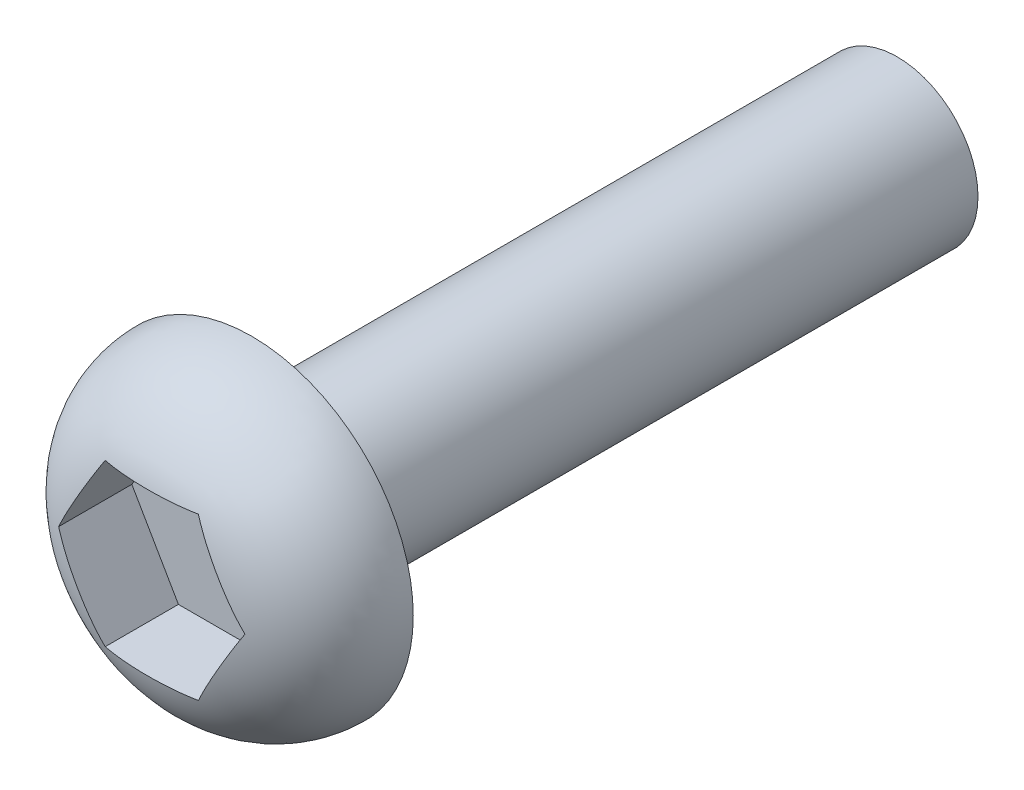
SolidWorks part; units mm, degrees
material "AISI 316 Stainless Steel Sheet (SS)"
ref_plane "Front Plane" through (0, 0, 0) normal (0, 0, 1) x (1, 0, 0)
ref_plane "Top Plane" through (0, 0, 0) normal (0, 1, 0) x (1, 0, 0)
ref_plane "Right Plane" through (0, 0, 0) normal (1, 0, 0) x (0, 0, -1)
sketch "Sketch1" plane through (0, 0, 0) normal (0, 0, 1) x (1, 0, 0)
  circle A0 centre (0, 0) radius 1.5
extrude "Boss-Extrude1" add sketch "Sketch1" along normal blind 12
sketch "Sketch2" plane through (0, 0, 12) normal (0, 0, 1) x (1, 0, 0)
  circle A0 centre (0, 0) radius 3
extrude "Boss-Extrude2" add sketch "Sketch2" along normal blind 2
sketch "Sketch3" plane through (0, 0, 14) normal (0, 0, 1) x (1, 0, 0)
  line L1 (-1.7321, 0) -> (-0.866, -1.5)
  line L2 (-0.866, -1.5) -> (0.866, -1.5)
  line L3 (0.866, -1.5) -> (1.7321, 0)
  line L4 (1.7321, 0) -> (0.866, 1.5)
  line L5 (0.866, 1.5) -> (-0.866, 1.5)
  line L6 (-0.866, 1.5) -> (-1.7321, 0)
  circle A0 centre (0, 0) radius 1.5 construction
extrude "Cut-Extrude1" cut sketch "Sketch3" against normal blind 1.5
fillet "Fillet1" radius 2 1 edges at (3, 0, 14)
